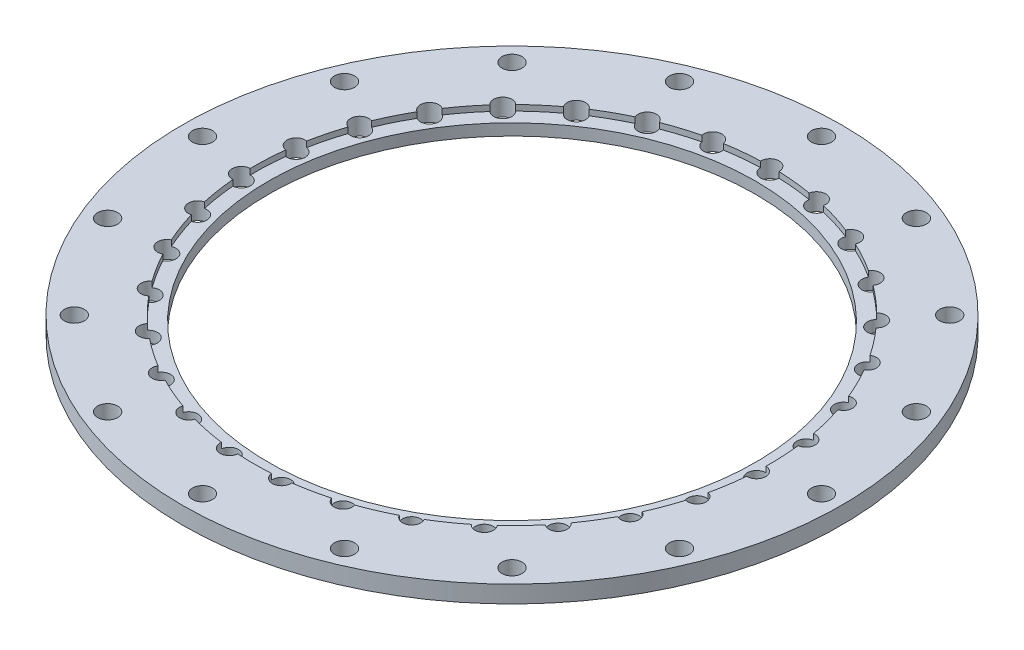
SolidWorks part; units mm, degrees
other "Markup1"
sketch "Sketch12" plane through (-57.5, 16, 57.5) normal (-0.5757, 0.7687, 0.2786) x (0.7628, 0.3823, 0.5216)
other "Markup2"
sketch "Sketch13" plane through (-57.5, 16, 57.5) normal (-0.5757, 0.7687, 0.2786) x (0.7628, 0.3823, 0.5216)
ref_plane "Front Plane" through (0, 0, 0) normal (0, 0, 1) x (1, 0, 0)
ref_plane "Top Plane" through (0, 0, 0) normal (0, 1, 0) x (1, 0, 0)
ref_plane "Right Plane" through (0, 0, 0) normal (1, 0, 0) x (0, 0, -1)
sketch "Sketch1" plane through (0, 0, 0) normal (0, 1, 0) x (1, 0, 0)
  line L0 (15.8389, 51.6249) -> (0, 0) construction
  line L1 (0, 0) -> (-4.5526, -44.7691) construction
  circle A0 centre (0, 0) radius 45
  circle A12 centre (0, 0) radius 57.5
  circle A13 centre (0, 0) radius 54 construction
  point P27 (0, 0)
  point P54 (0, 0)
  dimension "D1" = 90
  dimension "D4" = 115
  dimension "D5" = 108
  dimension "D8" = 11.25
extrude "Boss-Extrude1" add sketch "Sketch1" along normal blind 13 contours A12 region at (-55.8737, 0, 0)
sketch "Sketch2" plane through (0, 0, 0) normal (0, -1, 0) x (1, 0, 0)
  circle A0 centre (0, 0) radius 57.5
  circle A1 centre (0, 0) radius 45
extrude "Boss-Extrude2" add sketch "Sketch2" along normal blind 1
sketch "Sketch3" plane through (0, -1, 0) normal (0, -1, 0) x (1, 0, 0)
  circle A0 centre (0, 0) radius 57.5
  circle A1 centre (0, 0) radius 42.5
  dimension "D1" = 85
extrude "Boss-Extrude3" add sketch "Sketch3" along normal blind 2
sketch "Sketch5" plane through (0, 13, 0) normal (0, 1, 0) x (1, 0, 0)
  circle A0 centre (0, 45) radius 3
  circle A1 centre (0, 0) radius 45 construction
  circle A2 centre (0, 0) radius 45 construction
  dimension "D1" = 6
extrude "Cut-Extrude2" cut sketch "Sketch5" against normal blind 13
fillet "Fillet4" radius 0.5 2 edges at (2.9983, 6.5, -44.9) (-2.9983, 6.5, -44.9)
sketch "Sketch10" plane through (0, 13, 0) normal (0, 1, 0) x (1, 0, 0)
  circle A0 centre (0, 0) radius 45
  circle A1 centre (0, 0) radius 57.5
extrude "Boss-Extrude4" add sketch "Sketch10" along normal blind 1
sketch "Sketch11" plane through (0, 14, 0) normal (0, 1, 0) x (1, 0, 0)
  circle A0 centre (0, 0) radius 42.5
  circle A1 centre (0, 0) radius 57.5
extrude "Boss-Extrude5" add sketch "Sketch11" along normal blind 2
sketch "Sketch7" plane through (0, 16, 0) normal (0, 1, 0) x (1, 0, 0)
  circle A0 centre (0, 45) radius 1.6
  arc A1 (3.4425, 44.8681) -> (-3.4425, 44.8681) centre (0, 0) ccw construction
  dimension "D1" = 3.2
extrude "Cut-Extrude3" cut sketch "Sketch7" against normal blind 23
pattern_circular "CirPattern3" count 31 over 360 about axis through (0, -3, 0) along (0, 1, 0) of "Cut-Extrude2", "Fillet4", "Cut-Extrude3"
sketch "Sketch4" plane through (0, 16, 0) normal (0, 1, 0) x (1, 0, 0)
  circle A0 centre (0, 0) radius 54 construction
  circle A1 centre (0, 54) radius 1.75
  circle A2 centre (20.6649, 49.8895) radius 1.75
  circle A3 centre (38.1838, 38.1838) radius 1.75
  circle A4 centre (49.8895, 20.6649) radius 1.75
  circle A5 centre (54, 0) radius 1.75
  circle A6 centre (49.8895, -20.6649) radius 1.75
  circle A7 centre (38.1838, -38.1838) radius 1.75
  circle A8 centre (20.6649, -49.8895) radius 1.75
  circle A9 centre (0, -54) radius 1.75
  circle A10 centre (-20.6649, -49.8895) radius 1.75
  circle A11 centre (-38.1838, -38.1838) radius 1.75
  circle A12 centre (-49.8895, -20.6649) radius 1.75
  circle A13 centre (-54, 0) radius 1.75
  circle A14 centre (-49.8895, 20.6649) radius 1.75
  circle A15 centre (-38.1838, 38.1838) radius 1.75
  circle A16 centre (-20.6649, 49.8895) radius 1.75
  circle A17 centre (0, 0) radius 45 construction
  point P38 (0, 0)
  point P102 (0, 0)
  dimension "D1" = 108
  dimension "D2" = 3.5
extrude "Cut-Extrude1" cut sketch "Sketch4" against normal blind 51
sketch "Sketch14" plane through (0, 0, 0) normal (0, 1, 0) x (1, 0, 0)
  circle A0 centre (0, 0) radius 84.7001
extrude "Cut-Extrude4" cut sketch "Sketch14" along normal blind 54
